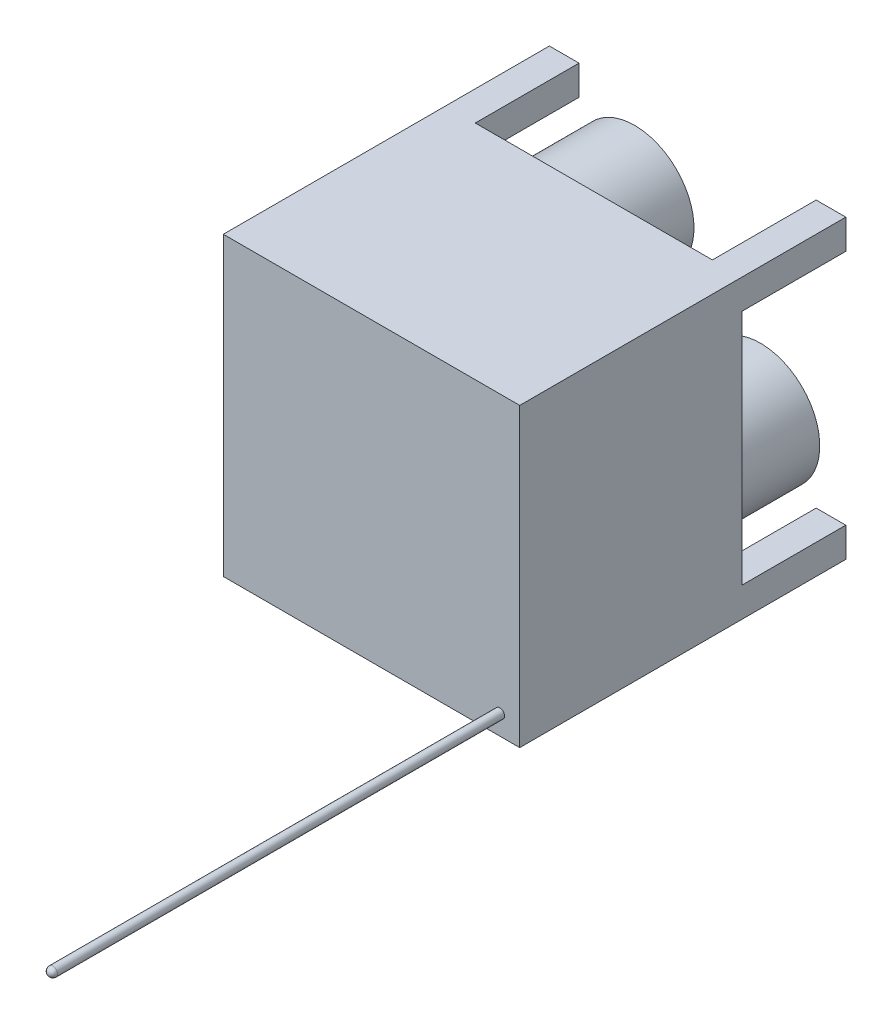
SolidWorks part; units mm, degrees
ref_plane "Front Plane" through (0, 0, 0) normal (0, 0, 1) x (1, 0, 0)
ref_plane "Top Plane" through (0, 0, 0) normal (0, 1, 0) x (1, 0, 0)
ref_plane "Right Plane" through (0, 0, 0) normal (1, 0, 0) x (0, 0, -1)
sketch "Sketch1" plane through (0, 0, 0) normal (0, 0, 1) x (1, 0, 0)
  line L1 (-50, -50) -> (50, -50)
  line L2 (-50, -50) -> (-50, 50)
  line L3 (-50, 50) -> (50, 50)
  line L4 (50, -50) -> (50, 50)
  line L5 (-50, -50) -> (50, 50) construction
  line L6 (-50, 50) -> (50, -50) construction
  point P0 (0, 0)
  dimension "D1" = 100
extrude "Boss-Extrude1" add sketch "Sketch1" along normal blind 110
ref_plane "Plane1" through (0, 0, 0) normal (-0.7071, 0.7071, 0) x (0.7071, 0.7071, 0)
ref_plane "Plane2" through (0, 0, 0) normal (-0.7071, -0.7071, 0) x (-0.7071, 0.7071, 0)
ref_axis "Axis1" through (0, 0, -5.5) along (0, 0, 1)
sketch "Sketch2" plane through (0, 0, 110) normal (0, 0, 1) x (1, 0, 0)
  circle A0 centre (43.2986, -43.3099) radius 1.5875
  dimension "D1" = 3.175
extrude "Boss-Extrude2" add sketch "Sketch2" along normal blind 152.4
fillet "Fillet1" radius 1.5875 1 edges at (44.8861, -43.3099, 262.4)
sketch "Sketch4" plane through (0, 0, 0) normal (0, 0, -1) x (-1, 0, 0)
  line L0 (-50, -50) -> (-50, 50) construction
  line L1 (-40, -120.6961) -> (40, -120.6961)
  line L2 (-40, -120.6961) -> (-40, 141.0972)
  line L3 (-40, 141.0972) -> (40, 141.0972)
  line L4 (40, -120.6961) -> (40, 141.0972)
  line L5 (-56.6627, -40) -> (94.7175, -40)
  line L6 (-56.6627, -40) -> (-56.6627, 40)
  line L7 (-56.6627, 40) -> (94.7175, 40)
  line L8 (94.7175, -40) -> (94.7175, 40)
  line L9 (50, 50) -> (50, -50) construction
  line L10 (-50, 50) -> (50, 50) construction
  line L11 (50, -50) -> (-50, -50) construction
  line M5 (-50, 50) -> (-50, -50)
  line M6 (-50, -50) -> (50, -50)
  line M7 (50, -50) -> (50, 50)
  line M8 (50, 50) -> (-50, 50)
  dimension "D1" = 10
  dimension "D2" = 10
  dimension "D3" = 10
  dimension "D4" = 10
extrude "Cut-Extrude2" cut sketch "Sketch4" against normal blind 35 contours L7 L4 L5 M7 | L7 L2 L5 L4 | L7 L5 L2 M5 | L5 L2 L4 M6 | L2 L7 L4 M8 region at (0, -45, 0) region at (45, 0, 0) region at (0, 0, 0) region at (-45, 0, 0) region at (0, 45, 0)
sketch "Sketch5" plane through (0, 0, 35) normal (0, 0, -1) x (-1, 0, 0)
  line L0 (-40, -40) -> (40, 40) construction
  circle A0 centre (-21.2132, -21.2132) radius 20
  circle A1 centre (21.2132, 21.2132) radius 20
  point P6 (0, 0)
  dimension "D3" = 40
  dimension "D1" = 30
  dimension "D2" = 30
extrude "Boss-Extrude3" add sketch "Sketch5" along normal up to surface (35 mm away) contours A1 L0 | L0 A1 | A0 region at (-15.2111, 27.2153, 35) region at (-27.2153, 15.2111, 35) up to face at (45, -45, 0)
equation "\"D2@Sketch4\"=\"D1@Sketch4\""
equation "\"D3@Sketch4\"=\"D1@Sketch4\""
equation "\"D4@Sketch4\"=\"D1@Sketch4\""
equation "\"D2@Sketch5\"=\"D1@Sketch5\""
